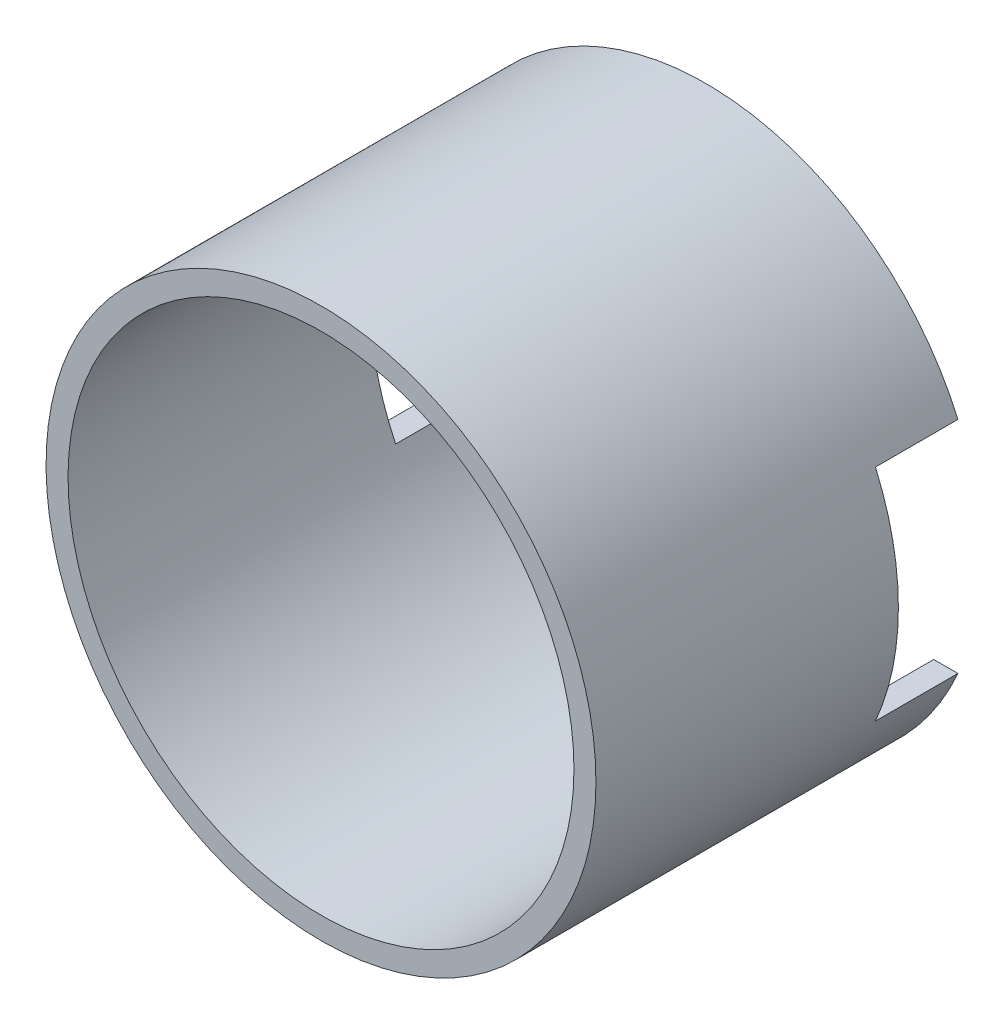
SolidWorks part; units mm, degrees
material "Простая углеродистая сталь"
ref_plane "Спереди" through (0, 0, 0) normal (0, 0, 1) x (1, 0, 0)
ref_plane "Сверху" through (0, 0, 0) normal (0, 1, 0) x (1, 0, 0)
ref_plane "Справа" through (0, 0, 0) normal (1, 0, 0) x (0, 0, -1)
sketch "Эскиз1" plane through (0, 0, 0) normal (0, 0, 1) x (1, 0, 0)
  circle A0 centre (0, 0) radius 15
  circle A1 centre (0, 0) radius 13.8
extrude "Бобышка-Вытянуть1" add sketch "Эскиз1" along normal blind 21
sketch "Эскиз2" plane through (0, 0, 0) normal (1, 0, 0) x (0, 0, -1)
  line L1 (4.5, -6) -> (-4.5, -6)
  line L2 (4.5, -6) -> (4.5, 6)
  line L3 (4.5, 6) -> (-4.5, 6)
  line L4 (-4.5, -6) -> (-4.5, 6)
  line L5 (4.5, -6) -> (-4.5, 6) construction
  line L6 (4.5, 6) -> (-4.5, -6) construction
  point P0 (0, 0)
extrude "Вырез-Вытянуть1" cut sketch "Эскиз2" against normal blind 21 and the other way blind 21
